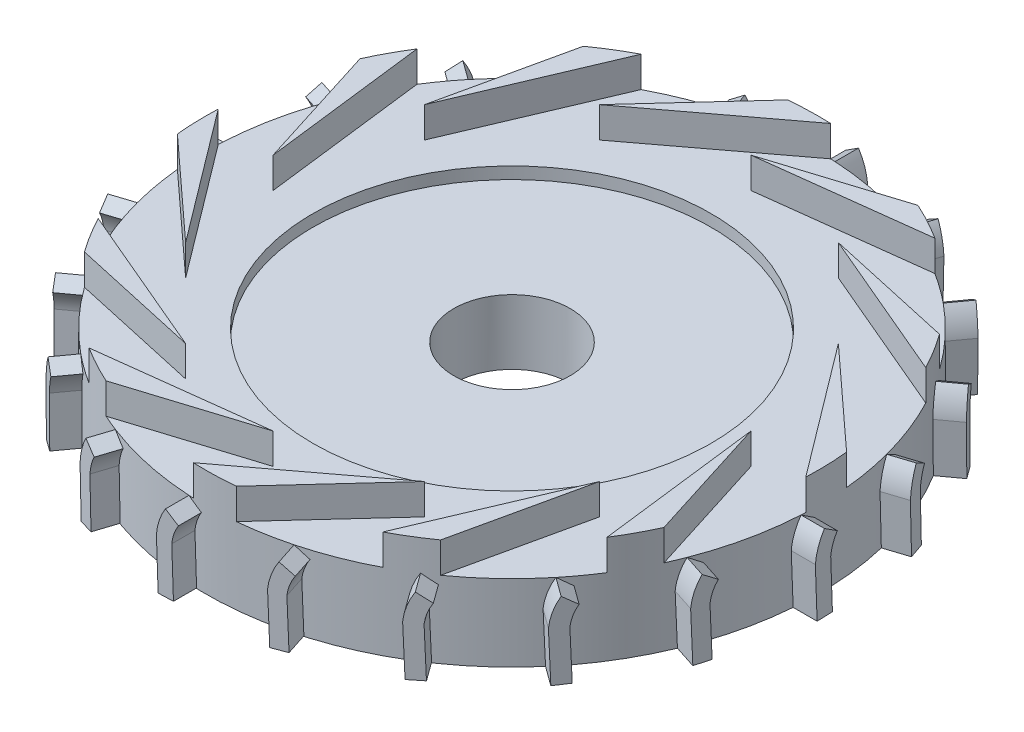
SolidWorks part; units mm, degrees
ref_plane "Front Plane" through (0, 0, 0) normal (0, 0, 1) x (1, 0, 0)
ref_plane "Top Plane" through (0, 0, 0) normal (0, 1, 0) x (1, 0, 0)
ref_plane "Right Plane" through (0, 0, 0) normal (1, 0, 0) x (0, 0, -1)
sketch "Sketch1" plane through (0, 0, 0) normal (1, 0, 0) x (0, 0, -1)
  line L0 (0, 26.2631) -> (0, -3.5886) construction
  line L1 (0, -3.5886) -> (-50.8, -3.5886)
  line L2 (-50.8, -3.5886) -> (-50.8, 9.1114)
  line L3 (-33.0001, 9.1114) -> (-50.8, 9.1114)
  line L4 (-33.0001, 9.1114) -> (-33.0001, 7.1515)
  line L5 (-33.0001, 7.1515) -> (0, 7.1515)
  line L6 (0, 7.1515) -> (0, -3.5886)
  dimension "D1" = 33.0001
  dimension "D2" = 50.8
  dimension "D3" = 1.96
  dimension "D4" = 12.7
revolve "Revolve1" add sketch "Sketch1" angle 360 about L0
sketch "Sketch2" plane through (0, 9.1114, 0) normal (0, 1, 0) x (1, 0, 0)
  line L8 (0, 39.6001) -> (19.9397, 39.6001) construction
  line L9 (0, 39.6001) -> (21.0453, 46.2356)
  line L10 (0, 39.6001) -> (27.1669, 42.9255)
  circle A0 centre (0, 0) radius 50.8 construction
  arc A1 (21.0453, 46.2356) -> (27.1669, 42.9255) centre (0, 0) cw
  circle A5 centre (0, 0) radius 33.0001 construction
  circle A7 centre (0, 0) radius 39.6001 construction
  point P9 (-2.4416, -40.4611)
  dimension "D1" = 66.0001
  dimension "D2" = 79.2001
  dimension "D3" = 17.5
extrude "Boss-Extrude1" add sketch "Sketch2" along normal blind 5.08
pattern_circular "CirPattern1" count 12 over 360 about axis through (0, 9.1114, 0) along (0, 1, 0) of "Boss-Extrude1"
ref_plane "Plane1" through (0, 0, 49.53) normal (0, 0, 1) x (1, 0, 0)
sketch "Sketch3" plane through (0, 0, 49.53) normal (0, 0, 1) x (1, 0, 0)
  line L0 (0, 0) -> (0, 9.7621) construction
  line L1 (0, -9.779) -> (0, 9.779) construction
  line L5 (-21.0453, 9.1114) -> (0, 9.1114) construction
  line L6 (-50.8, -3.5886) -> (50.8, -3.5886) construction
  line L7 (-4.3287, 4.6923) -> (-4.0403, -3.5886)
  line L10 (-1.7845, 4.6163) -> (-1.5018, -3.5001)
  line L11 (-0.685, 7.735) -> (-2.8198, 9.1114)
  line L12 (-4.0403, -3.5886) -> (-1.5018, -3.5001)
  arc A4 (-2.8198, 9.1114) -> (-4.3287, 4.6923) centre (5.3144, 3.8668) ccw
  arc A5 (-0.685, 7.735) -> (-1.7845, 4.6163) centre (5.3144, 3.8668) ccw
  dimension "D1" = 2.54
extrude "Boss-Extrude2" add sketch "Sketch3" along normal blind 5.08 and the other way blind 0.254
pattern_circular "CirPattern16" count 20 over 360 about axis through (0, -3.5886, 0) along (0, 1, 0) of "Boss-Extrude2"
sketch "Sketch4" plane through (0, 7.1515, 0) normal (0, 1, 0) x (1, 0, 0)
  circle A0 centre (0, 0) radius 9.652
  dimension "D1" = 19.304
extrude "Cut-Extrude1" cut sketch "Sketch4" against normal up to next
sketch "Sketch5" plane through (0, -3.5886, 0) normal (0, -1, 0) x (-1, 0, 0)
  circle A0 centre (0, 0) radius 38.1
  dimension "D1" = 76.2
extrude "Cut-Extrude2" cut sketch "Sketch5" against normal blind 7.62
sketch "Sketch6" plane through (0, 4.0314, 0) normal (0, -1, 0) x (1, 0, 0)
  circle A0 centre (0, 0) radius 19.05
  circle A1 centre (0, 0) radius 9.652 construction
  circle A2 centre (0, 0) radius 9.652
  dimension "D1" = 38.1
extrude "Boss-Extrude3" add sketch "Sketch6" along normal up to surface (7.62 mm away) up to face at (0, -3.5886, -38.1)
